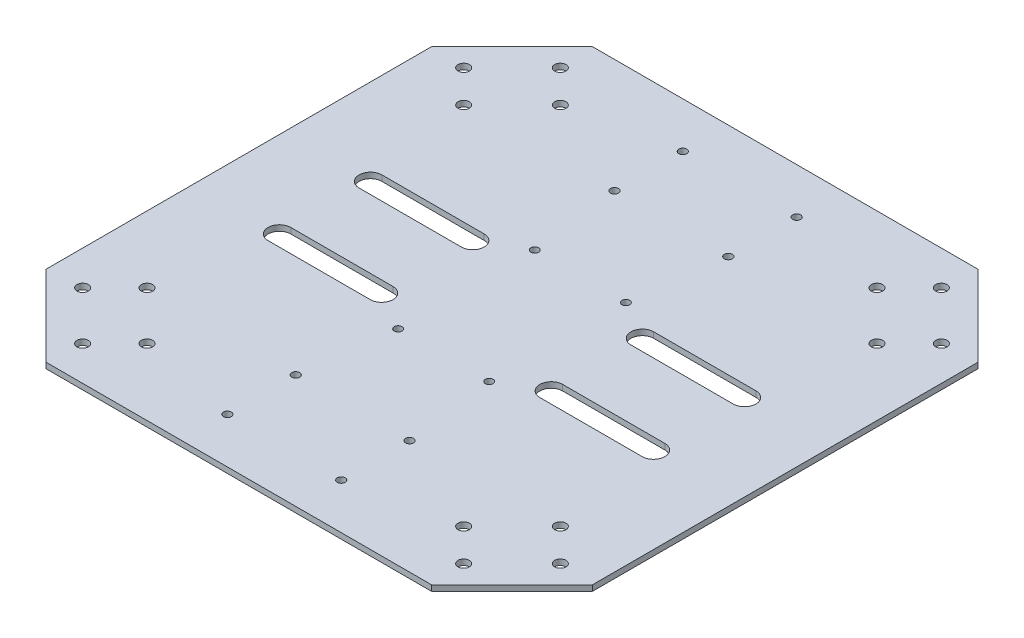
SolidWorks part; units mm, degrees
ref_plane "Front Plane" through (0, 0, 0) normal (0, 0, 1) x (1, 0, 0)
ref_plane "Top Plane" through (0, 0, 0) normal (0, 1, 0) x (1, 0, 0)
ref_plane "Right Plane" through (0, 0, 0) normal (1, 0, 0) x (0, 0, -1)
sketch "Sketch1" plane through (0, 0, 0) normal (0, 1, 0) x (1, 0, 0)
  line L0 (-61.766, 6.7551) -> (-16.8648, 51.6564)
  line L1 (-61.766, 51.6564) -> (243.034, 51.6564)
  line L2 (-61.766, 51.6564) -> (-61.766, -253.1436)
  line L3 (-61.766, -253.1436) -> (243.034, -253.1436)
  line L4 (243.034, 51.6564) -> (243.034, -253.1436)
  line L5 (90.634, 95.069) -> (90.634, -294.9418) construction
  line L6 (-86.5248, -100.7436) -> (277.558, -100.7436) construction
  line L7 (243.034, 6.7551) -> (198.1327, 51.6564)
  line L8 (243.034, -208.2424) -> (198.1327, -253.1436)
  line L9 (-61.766, -208.2424) -> (-16.8648, -253.1436)
  line L10 (137.9303, -75.3436) -> (194.9471, -75.3436) construction
  line L11 (137.9303, -68.9936) -> (194.9471, -68.9936)
  line L12 (137.9303, -81.6936) -> (194.9471, -81.6936)
  line L13 (137.9303, -126.1436) -> (194.9471, -126.1436) construction
  line L14 (137.9303, -132.4936) -> (194.9471, -132.4936)
  line L15 (137.9303, -119.7936) -> (194.9471, -119.7936)
  line L16 (43.3376, -126.1436) -> (-13.6792, -126.1436) construction
  line L17 (43.3376, -132.4936) -> (-13.6792, -132.4936)
  line L18 (43.3376, -119.7936) -> (-13.6792, -119.7936)
  line L19 (43.3376, -75.3436) -> (-13.6792, -75.3436) construction
  line L20 (43.3376, -68.9936) -> (-13.6792, -68.9936)
  line L21 (43.3376, -81.6936) -> (-13.6792, -81.6936)
  arc A0 (137.9303, -68.9936) -> (137.9303, -81.6936) centre (137.9303, -75.3436) ccw
  arc A1 (194.9471, -81.6936) -> (194.9471, -68.9936) centre (194.9471, -75.3436) ccw
  arc A2 (137.9303, -132.4936) -> (137.9303, -119.7936) centre (137.9303, -126.1436) cw
  arc A3 (194.9471, -119.7936) -> (194.9471, -132.4936) centre (194.9471, -126.1436) cw
  arc A4 (43.3376, -132.4936) -> (43.3376, -119.7936) centre (43.3376, -126.1436) ccw
  arc A5 (-13.6792, -119.7936) -> (-13.6792, -132.4936) centre (-13.6792, -126.1436) ccw
  arc A6 (43.3376, -68.9936) -> (43.3376, -81.6936) centre (43.3376, -75.3436) cw
  arc A7 (-13.6792, -81.6936) -> (-13.6792, -68.9936) centre (-13.6792, -75.3436) cw
  point P8 (90.634, 51.6564)
  point P11 (-61.766, -100.7436)
  point P18 (166.4387, -75.3436)
  point P27 (166.4387, -126.1436)
  point P34 (14.8292, -126.1436)
  point P41 (14.8292, -75.3436)
  dimension "D6" = 6.35
  dimension "D1" = 304.8
  dimension "D2" = 304.8
  dimension "D3" = 45
  dimension "D4" = 63.5
  dimension "D5" = 38.1
extrude "Boss-Extrude1" add sketch "Sketch1" along normal blind 3.175 contours L2 L9 L3 L8 L4 L7 L1 L0 A5 L18 A4 L17 A1 L12 A0 L11 L15 A3 L14 A2 L21 A7 L20 A6 region at (90.634, 0, 100.7436)
sketch "Sketch2" plane through (0, 3.175, 0) normal (0, 1, 0) x (1, 0, 0)
  line L7 (90.634, 51.6564) -> (90.634, -253.1436) construction
  line L8 (-16.8648, 51.6564) -> (198.1327, 51.6564) construction
  line L9 (-16.8648, -253.1436) -> (198.1327, -253.1436) construction
  line L10 (-61.766, -100.7436) -> (243.034, -100.7436) construction
  line L11 (-61.766, 6.7551) -> (-61.766, -208.2424) construction
  line L12 (243.034, 6.7551) -> (243.034, -208.2424) construction
  circle A0 centre (-15.6273, 32.4584) radius 3.175
  circle A1 centre (2.3332, 14.4979) radius 3.175
  circle A2 centre (-24.6076, -12.4429) radius 3.175
  circle A3 centre (-42.5681, 5.5176) radius 3.175
  circle A4 centre (205.8755, -12.4429) radius 3.175
  circle A5 centre (223.836, 5.5176) radius 3.175
  circle A6 centre (178.9347, 14.4979) radius 3.175
  circle A7 centre (196.8952, 32.4584) radius 3.175
  circle A8 centre (-24.6076, -189.0444) radius 3.175
  circle A9 centre (-42.5681, -207.0049) radius 3.175
  circle A10 centre (-15.6273, -233.9457) radius 3.175
  circle A11 centre (2.3332, -215.9852) radius 3.175
  circle A12 centre (223.836, -207.0049) radius 3.175
  circle A13 centre (196.8952, -233.9457) radius 3.175
  circle A14 centre (178.9347, -215.9852) radius 3.175
  circle A15 centre (205.8755, -189.0444) radius 3.175
  dimension "D3" = 6.35
  dimension "D4" = 6.35
  dimension "D5" = 6.35
  dimension "D6" = 6.35
  dimension "D1" = 25.4
  dimension "D2" = 38.1
extrude "Cut-Extrude1" cut sketch "Sketch2" against normal blind 6.35
sketch "Sketch3" plane through (0, 3.175, 0) normal (0, 1, 0) x (1, 0, 0)
  circle A0 centre (65.234, -62.6436) radius 2.159
  circle A1 centre (116.034, -62.6436) radius 2.159
  circle A2 centre (65.234, -138.8436) radius 2.159
  circle A3 centre (116.034, -138.8436) radius 2.159
  dimension "D3" = 4.318
  dimension "D4" = 4.318
  dimension "D5" = 4.318
  dimension "D6" = 4.318
  dimension "D1" = 50.8
  dimension "D2" = 76.2
extrude "Cut-Extrude2" cut sketch "Sketch3" against normal blind 6.35
sketch "Sketch4" plane through (0, 3.175, 0) normal (0, 1, 0) x (1, 0, 0)
  line L0 (90.634, 51.6564) -> (90.634, -36.4614) construction
  line L1 (-16.8648, 51.6564) -> (198.1327, 51.6564) construction
  line L2 (-61.766, -100.7436) -> (257.447, -100.7436) construction
  line L3 (-61.766, 6.7551) -> (-61.766, -208.2424) construction
  circle A0 centre (58.884, 26.2564) radius 2.2225
  circle A1 centre (122.384, 26.2564) radius 2.2225
  circle A2 centre (58.884, -11.8436) radius 2.2225
  circle A3 centre (122.384, -11.8436) radius 2.2225
  circle A4 centre (122.384, -189.6436) radius 2.2225
  circle A5 centre (58.884, -189.6436) radius 2.2225
  circle A6 centre (122.384, -227.7436) radius 2.2225
  circle A7 centre (58.884, -227.7436) radius 2.2225
  dimension "D1" = 4.445
  dimension "D2" = 4.445
  dimension "D3" = 4.445
  dimension "D4" = 4.445
  dimension "D5" = 63.5
  dimension "D6" = 38.1
  dimension "D7" = 31.75
  dimension "D8" = 25.4
extrude "Cut-Extrude3" cut sketch "Sketch4" against normal through all
